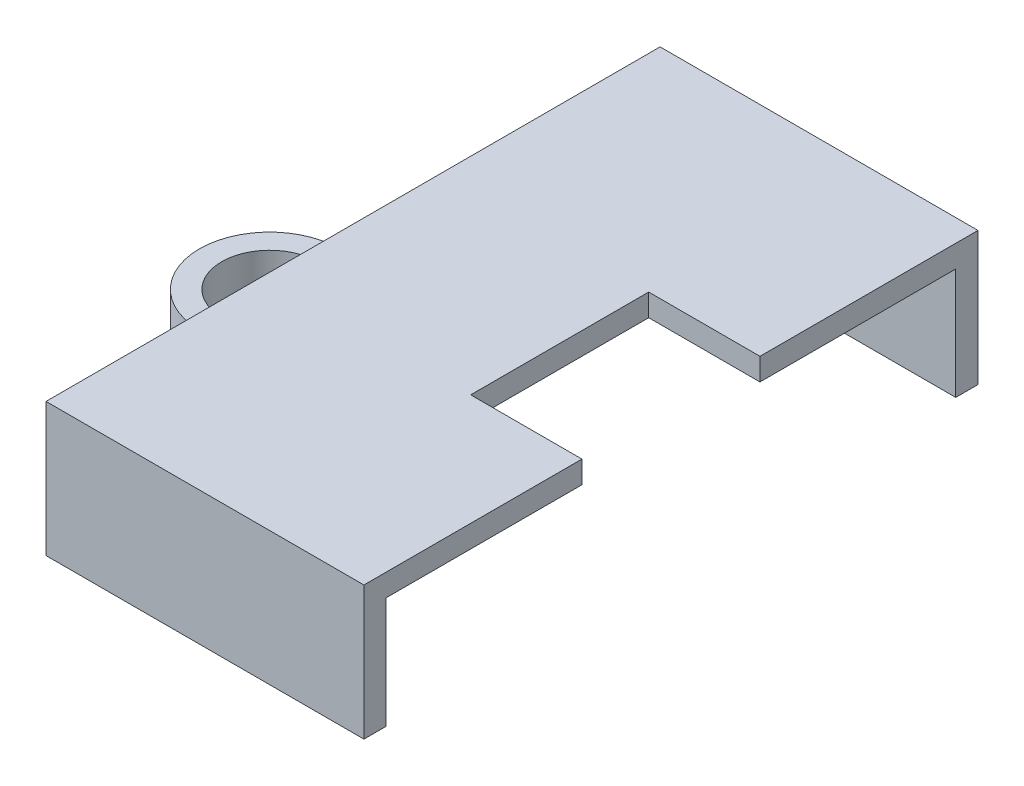
SolidWorks part; units mm, degrees
material "PTFE (teflon)"
ref_plane "Front Plane" through (0, 0, 0) normal (0, 0, 1) x (1, 0, 0)
ref_plane "Top Plane" through (0, 0, 0) normal (0, 1, 0) x (1, 0, 0)
ref_plane "Right Plane" through (0, 0, 0) normal (1, 0, 0) x (0, 0, -1)
sketch "Sketch1" plane through (0, 0, 0) normal (0, 1, 0) x (1, 0, 0)
  line L0 (0, 2.1526) -> (4.75, 2.1526)
  line L1 (4.75, 2.1526) -> (4.75, 12.7963)
  line L2 (4.75, 12.7963) -> (17.035, 12.7963)
  line L3 (17.035, 12.7963) -> (17.035, 4)
  line L4 (17.035, -12.7963) -> (4.75, -12.7963)
  line L5 (4.75, -12.7963) -> (4.75, -2.1526)
  line L6 (4.75, -2.1526) -> (0, -2.1526)
  line L7 (18.035, 4) -> (13.035, 4)
  line L8 (13.035, 4) -> (13.035, -4)
  line L9 (13.035, -4) -> (18.035, -4)
  line L10 (0, 2.1526) -> (0, 3.1526)
  line L11 (0, 3.1526) -> (3.75, 3.1526)
  line L12 (3.75, 3.1526) -> (3.75, 13.7963)
  line L13 (3.75, 13.7963) -> (18.035, 13.7963)
  line L14 (18.035, 13.7963) -> (18.035, 4)
  line L15 (18.035, -13.7963) -> (3.75, -13.7963)
  line L16 (3.75, -13.7963) -> (3.75, -3.1526)
  line L17 (3.75, -3.1526) -> (0, -3.1526)
  line L18 (0, -3.1526) -> (0, -2.1526)
  line L19 (18.035, 5) -> (12.035, 5)
  line L20 (12.035, 5) -> (12.035, -5)
  line L21 (12.035, -5) -> (18.035, -5)
  line L22 (18.035, -4) -> (18.035, -13.7963)
  line L23 (17.035, -4) -> (17.035, -12.7963)
  line L24 (4.75, 2.1526) -> (4.75, -2.1526)
  line L25 (17.035, -12.7963) -> (18.035, -12.7963)
  line L26 (17.035, 12.7963) -> (18.035, 12.7963)
  line L27 (3.75, 3.1526) -> (3.75, 2.1526)
  line L28 (3.75, -3.1526) -> (3.75, -2.1526)
  line L29 (3.75, 2.1526) -> (3.75, -2.1526)
  circle A0 centre (0, 0) radius 2.1526
  circle A1 centre (0, 0) radius 3.1526
  point P11 (13.035, 0)
  point P27 (12.035, 0)
  point P29 (15.535, 4)
  dimension "D1" = 4.3053
  dimension "D2" = 1
  dimension "D6" = 5
  dimension "D7" = 8
  dimension "D4" = 1
  dimension "D5" = 1
  dimension "D8" = 1
  dimension "D10" = 27.5927
  dimension "D11" = 1
  dimension "D12" = 1
  dimension "D9" = 14.285
  dimension "D3" = 3.75
extrude "Boss-Extrude1" add sketch "Sketch1" along normal blind 1 from offset 5 contours A1 L0 L1 L2 L3 L19 L14 L13 L12 L11 | L14 L19 L3 L7 | L23 L9 L8 L7 L3 L19 L20 L21 | L9 L23 L21 L22 | A1 L6 L5 L4 L23 L21 L20 L19 L3 L2 L1 L0 | L23 L25 L22 L21 | L26 L3 L19 L14 | A1 L17 L16 L15 L22 L25 L4 L5 L6 | L0 L29 L6 L24 region at (3.9343, 0, -2.6526) region at (4.25, 0, 0) region at (10.2037, 0, 0) region at (4.25, 0, 2.3369) region at (17.535, 0, -8.8982) region at (17.535, 0, -4.5) region at (16.9232, 0, -4.5) region at (17.535, 0, 8.8982) region at (17.535, 0, 4.5)
extrude "Boss-Extrude2" add sketch "Sketch1<4>" along normal up to surface (5 mm away) contours L0 L29 L6 L24 | L12 L27 L0 L1 L2 L26 L14 L13 | L28 L16 L15 L22 L25 L4 L5 L6 region at (3.9343, 0, -2.6526) region at (4.25, 0, 0) region at (4.25, 0, 2.3369) up to face at (13.2138, 5, 0)
sketch "Sketch1<4>" plane through (0, 0, 0) normal (0, 1, 0) x (1, 0, 0) same geometry as "Sketch1"
extrude "Boss-Extrude3" add sketch "Sketch1<5>" along normal blind 1.5875 contours A1 L0 L27 L11 | A1 L6 L29 L0 | A1 L17 L28 L6 | L6 A1 L0 A0 | L10 A1 L18 A0 | L0 A1 L10 | L18 A1 L6 region at (3.2831, 0, 0) region at (2.605, 0, -2.722) region at (2.2177, 0, 0) region at (0.8855, 0, -2.5586) region at (2.605, 0, 2.722) region at (-2.2231, 0, 0) region at (0.8855, 0, 2.5586)
sketch "Sketch1<5>" plane through (0, 0, 0) normal (0, 1, 0) x (1, 0, 0) same geometry as "Sketch1"
equation "\"D4@Sketch1\"=\"D2@Sketch1\""
equation "\"D5@Sketch1\"=\"D4@Sketch1\""
equation "\"D8@Sketch1\"=\"D4@Sketch1\""
equation "\"D11@Sketch1\"=\"D8@Sketch1\""
equation "\"D12@Sketch1\"=\"D11@Sketch1\""
equation "\"D9@Sketch1\"=12.21mm +2.15/2 +1"
